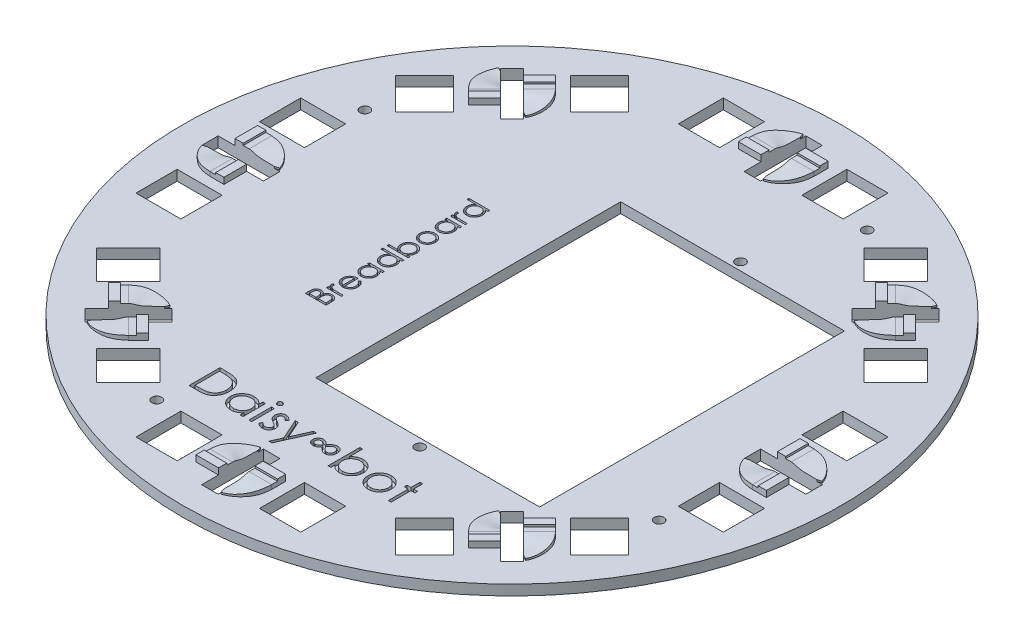
SolidWorks part; units mm, degrees
ref_plane "Front" through (0, 0, 0) normal (0, 0, 1) x (1, 0, 0)
ref_plane "Top" through (0, 0, 0) normal (0, 1, 0) x (1, 0, 0)
ref_plane "Right" through (0, 0, 0) normal (1, 0, 0) x (0, 0, -1)
sketch "Sketch1" plane through (0, 0, 0) normal (0, 1, 0) x (1, 0, 0)
  circle A0 centre (0, 0) radius 101.6
  dimension "D1" = 203.2
extrude "Base" add sketch "Sketch1" along normal blind 3.175 contours A0
sketch "Sketch2" plane through (0, 3.175, 0) normal (0, 1, 0) x (1, 0, 0)
  line L1 (-2.54, -93.1333) -> (2.54, -93.1333)
  line L2 (-2.54, -93.1333) -> (-2.54, -74.0833)
  line L3 (-2.54, -74.0833) -> (2.54, -74.0833)
  line L4 (2.54, -93.1333) -> (2.54, -74.0833)
  point P4 (0, -74.0833)
  dimension "D1" = 5.08
  dimension "D2" = 19.05
  dimension "D3" = 93.1333
extrude "Cut-Extrude1" cut sketch "Sketch2" against normal up to next and the other way through all contours L1 L4 L3 L2
sketch "Sketch4" plane through (0, 3.175, 0) normal (0, 1, 0) x (1, 0, 0)
  line L0 (0, -83.6083) -> (-2.9434, -74.5495) construction
  line L1 (-2.9434, -74.5495) -> (0, -83.6083) construction
  line L2 (0, -83.6083) -> (-5.5987, -75.9024) construction
  line L3 (0, -83.6083) -> (-7.7059, -78.0097) construction
  line L4 (0, -83.6083) -> (-9.0588, -80.6649) construction
  line L5 (0, -83.6083) -> (-9.525, -83.6083) construction
  line L9 (2.54, -74.0833) -> (-2.54, -74.0833) construction
  line L10 (2.54, -74.0833) -> (2.54, -93.1333) construction
  line L11 (-2.54, -74.0833) -> (-2.54, -93.1333) construction
  line L12 (2.54, -93.1333) -> (-2.54, -93.1333) construction
  circle A0 centre (0, -83.6083) radius 9.525 construction
  point P16 (0, -74.0833)
  point P19 (2.54, -83.6083)
  dimension "D1" = 18
  dimension "D2" = 18
  dimension "D3" = 18
  dimension "D4" = 18
  dimension "D5" = 18
ref_plane "Plane1" through (-24.5719, 0, 7.9839) normal (0.9511, 0, -0.309) x (-0.309, 0, -0.9511)
ref_plane "Plane2" through (-39.7581, 0, 28.886) normal (0.809, 0, -0.5878) x (-0.5878, 0, -0.809)
ref_plane "Plane3" through (-39.7581, 0, 54.7224) normal (0.5878, 0, -0.809) x (-0.809, 0, -0.5878)
ref_plane "Plane4" through (-24.5719, 0, 75.6244) normal (0.309, 0, -0.9511) x (-0.9511, 0, -0.309)
ref_plane "Plane5" through (0, 0, 83.6083) normal (0, 0, -1) x (-1, 0, 0)
sketch "Sketch5" plane through (-24.5719, 0, 7.9839) normal (0.9511, 0, -0.309) x (-0.309, 0, -0.9511)
  line L0 (-69.6725, 3.175) -> (-87.7902, 3.175) construction
  line L1 (-71.2966, 3.175) -> (-69.9913, 3.175)
  line L2 (-71.2966, 3.175) -> (-71.2966, 3.683)
  line L3 (-71.2966, 3.683) -> (-69.9913, 3.683)
  line L4 (-69.9913, 3.175) -> (-69.9913, 3.683)
  dimension "D2" = 0.508
sketch "Sketch6" plane through (-39.7581, 0, 28.886) normal (0.809, 0, -0.5878) x (-0.5878, 0, -0.809)
  line L0 (-58.4417, 3.175) -> (-73.8535, 3.175) construction
  line L1 (-63.3193, 3.175) -> (-58.1156, 3.175)
  line L2 (-63.3193, 3.175) -> (-63.3193, 3.775)
  line L3 (-63.3193, 3.775) -> (-58.1156, 3.775)
  line L4 (-58.1156, 3.175) -> (-58.1156, 3.775)
  dimension "D2" = 0.6
sketch "Sketch7" plane through (-39.7581, 0, 54.7224) normal (0.5878, 0, -0.809) x (-0.809, 0, -0.5878)
  line L0 (-41.4902, 3.175) -> (-52.6875, 3.175) construction
  line L1 (-46.0041, 3.175) -> (-39.6187, 3.175)
  line L2 (-46.0041, 3.175) -> (-46.0041, 4.075)
  line L3 (-46.0041, 4.075) -> (-39.6187, 4.075)
  line L4 (-39.6187, 3.175) -> (-39.6187, 4.075)
  dimension "D2" = 0.9
sketch "Sketch10" plane through (-24.5719, 0, 75.6244) normal (0.309, 0, -0.9511) x (-0.9511, 0, -0.309)
  line L0 (-25.8364, 3.175) -> (-16.7776, 3.175) construction
  line L1 (-23.1657, 3.175) -> (-16.3114, 3.175)
  line L2 (-23.1657, 3.175) -> (-23.1657, 4.375)
  line L3 (-23.1657, 4.375) -> (-16.3114, 4.375)
  line L4 (-16.3114, 3.175) -> (-16.3114, 4.375)
  dimension "D3" = 1.2
sketch "Sketch11" plane through (0, 0, 83.6083) normal (0, 0, -1) x (-1, 0, 0)
  line L0 (0, 3.175) -> (9.525, 3.175) construction
  line L1 (2.54, 3.175) -> (9.525, 3.175)
  line L2 (2.54, 3.175) -> (2.54, 4.475)
  line L3 (2.54, 4.475) -> (9.525, 4.475)
  line L4 (9.525, 3.175) -> (9.525, 4.475)
  dimension "D3" = 1.3
loft "Loft1" add profiles "Sketch5", "Sketch6", "Sketch7", "Sketch10", "Sketch11" connector at (-2.54, 3.683, 75.791) connector at (-2.54, 3.775, 80.1123) connector at (-2.54, 4.075, 81.7629) connector at (-2.54, 4.375, 82.783) connector at (-2.54, 4.475, 83.6083)
sketch "Sketch13" plane through (-104.9799, 0, 83.6083) normal (0, 0, -1) x (-1, 0, 0)
  line L6 (-95.4549, 3.175) -> (-102.4399, 3.175)
  line L7 (-95.4549, 3.175) -> (-95.4549, 4.475)
  line L8 (-95.4549, 4.475) -> (-102.4399, 4.475)
  line L9 (-102.4399, 3.175) -> (-102.4399, 4.475)
extrude "Boss-Extrude4" add sketch "Sketch13" against normal blind 1.7907
sketch "Sketch25" plane through (0, 0, 85.399) normal (0, 0, 1) x (1, 0, 0)
  line L0 (-9.525, 4.475) -> (-2.54, 4.475) construction
  line L1 (-9.525, 3.175) -> (-2.54, 3.175)
  line L2 (-9.525, 3.175) -> (-9.525, 5.075)
  line L3 (-9.525, 5.075) -> (-2.54, 5.075)
  line L4 (-2.54, 3.175) -> (-2.54, 5.075)
  dimension "D1" = 0.6
extrude "Boss-Extrude5" add sketch "Sketch25" along normal blind 2.54
sketch "Sketch14" plane through (-2.54, 0, 0) normal (1, 0, 0) x (0, 0, -1)
  line L0 (-83.6083, 3.175) -> (-83.6083, 0) construction
  line L1 (-74.0833, 0) -> (-93.1333, 0) construction
ref_plane "Plane6" through (0, 0, 0) normal (1, 0, 0) x (0, 0, -1)
sketch "Sketch15" plane through (0, 0, 0) normal (1, 0, 0) x (0, 0, -1)
  line L0 (-83.6083, 0) -> (-83.6083, 3.175) construction
pattern_circular "CirPattern1" count 2 over 360 about axis through (0, 0, 83.6083) along (0, 1, 0) of "Loft1", "Boss-Extrude5", "Boss-Extrude4" reverse direction yes
ref_axis "Axis1" through (0, 50, 0) along (0, -1, 0)
pattern_circular "CirPattern5" count 8 over 360 about axis through (0, 50, 0) along (0, -1, 0) of "CirPattern1", "Cut-Extrude1"
sketch "Sketch18" plane through (0, 3.175, 0) normal (0, 1, 0) x (1, 0, 0)
  line L4 (0, -101.6) -> (0, 101.6) construction
  line L5 (0, -1.7463) -> (0, 1.7463) construction
  line L9 (-13.5, -47) -> (55.5, -47)
  line L10 (-13.5, -47) -> (-13.5, 47)
  line L11 (-13.5, 47) -> (55.5, 47)
  line L12 (55.5, -47) -> (55.5, 47)
  circle A8 centre (0, 0) radius 101.6 construction
  point P0 (55.5, 0)
  point P28 (48.26, 44.45)
  dimension "D1" = 13.5
  dimension "D3" = 94
  dimension "D4" = 69
sketch "Sketch19" plane through (0, 3.175, 0) normal (0, 1, 0) x (1, 0, 0)
  line L0 (-32.0765, -77.4396) -> (0, 0) construction
  line L1 (0, -101.6) -> (0, 101.6) construction
  circle A1 centre (-32.0765, -77.4396) radius 1.5
  circle A4 centre (0, 0) radius 101.6 construction
  dimension "D4" = 3
  dimension "D6" = 83.82
  dimension "D5" = 22.5
extrude "Cut-Extrude2" cut sketch "Sketch19" against normal through all
pattern_circular "CirPattern7" count 4 over 360 about axis through (0, 50, 0) along (0, -1, 0) of "Cut-Extrude2"
sketch "Sketch23" plane through (0, 3.175, 0) normal (0, 1, 0) x (1, 0, 0)
  line L9 (-2.54, -87.939) -> (-2.54, -93.1333) construction
  line L10 (-25.4, -76.6805) -> (-12.7, -76.6805)
  line L11 (-25.4, -76.6805) -> (-25.4, -90.5362)
  line L16 (-25.4, -90.5362) -> (-12.7, -90.5362)
  line L17 (-12.7, -76.6805) -> (-12.7, -90.5362)
  line L19 (2.54, -74.0833) -> (2.54, -79.2776) construction
  line L20 (0, -50) -> (0, 50) construction
  line L21 (12.7, -76.6805) -> (12.7, -90.5362)
  line L22 (25.4, -90.5362) -> (12.7, -90.5362)
  line L23 (25.4, -76.6805) -> (25.4, -90.5362)
  line L24 (25.4, -76.6805) -> (12.7, -76.6805)
  point P8 (-2.54, -90.5362)
  point P9 (2.54, -76.6805)
  dimension "D1" = 12.7
  dimension "D2" = 10.16
extrude "Cut-Extrude6" cut sketch "Sketch23" against normal through all
pattern_circular "CirPattern8" count 8 over 360 about axis through (0, 50, 0) along (0, -1, 0) of "Cut-Extrude6"
sketch "Sketch17" plane through (0, 3.175, 0) normal (0, 1, 0) x (1, 0, 0)
  line L0 (33.02, -68.58) -> (-33.02, -68.58) construction
  line L1 (2.54, -74.0833) -> (-2.54, -74.0833) construction
  point P3 (0, -68.58)
  point P7 (0, -74.0833)
  dimension "D2" = 68.58
  dimension "D1" = 66.04
sketch "Sketch16" plane through (0, 3.175, 0) normal (0, 1, 0) x (1, 0, 0)
  line L0 (33.02, -68.58) -> (-33.02, -68.58) construction
  text T0 "Daisy∞bot\r\n" font "Century Gothic" height in points 36
extrude "Cut-Extrude4" cut sketch "Sketch16" against normal blind 1.27
sketch "Sketch22" plane through (0, 3.175, 0) normal (0, 1, 0) x (1, 0, 0)
  line L0 (-31.3017, 25.1735) -> (-31.3017, -33.6024) construction
  text T0 "Breadboard"
extrude "Cut-Extrude5" cut sketch "Sketch22" against normal blind 1.27
extrude "Cut-Extrude7" cut sketch "Sketch18" against normal through all
sketch "Sketch26" plane through (0, 3.175, 0) normal (0, 1, 0) x (1, 0, 0)
  line L0 (-13.5, -47) -> (55.5, -47) construction
  line L1 (-50, 0) -> (50, 0) construction
  circle A0 centre (21, -49.45) radius 1.5
  circle A2 centre (21, 49.45) radius 1.5
  point P4 (21, -47)
  dimension "D1" = 3
  dimension "D2" = 2.45
extrude "Cut-Extrude8" cut sketch "Sketch26" against normal through all
